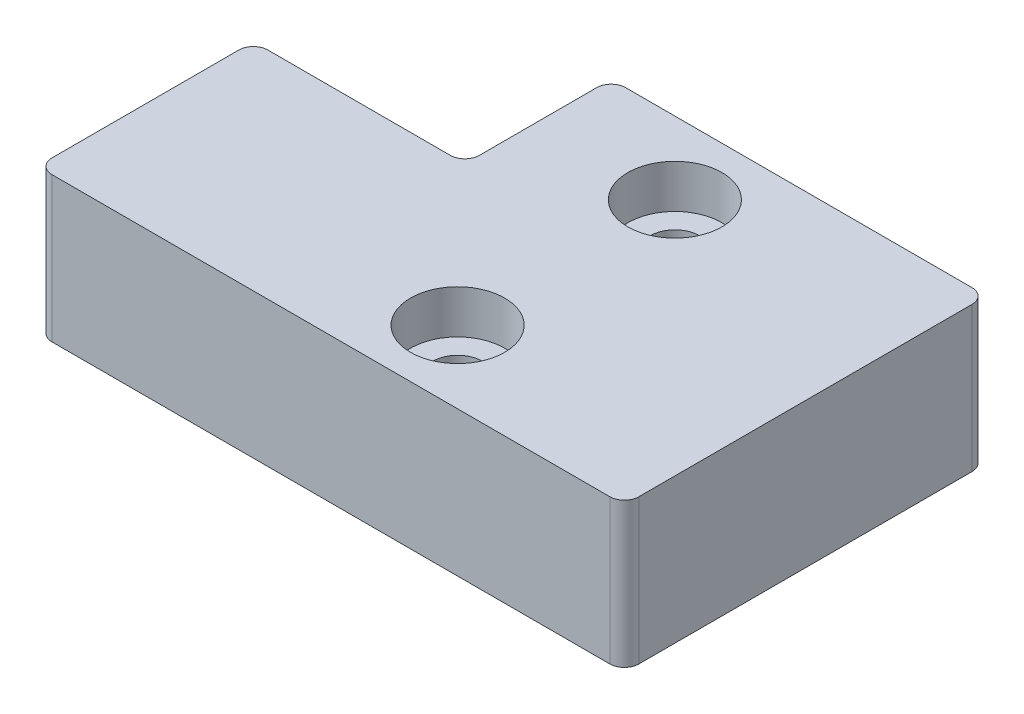
SolidWorks part; units mm, degrees
ref_plane "Front Plane" through (0, 0, 0) normal (0, 0, 1) x (1, 0, 0)
ref_plane "Top Plane" through (0, 0, 0) normal (0, 1, 0) x (1, 0, 0)
ref_plane "Right Plane" through (0, 0, 0) normal (1, 0, 0) x (0, 0, -1)
sketch "Sketch1" plane through (0, 0, 0) normal (0, 1, 0) x (1, 0, 0)
  line L0 (0, 0) -> (40.51, 0)
  line L1 (40.51, 0) -> (40.51, 25)
  line L2 (40.51, 25) -> (14.6, 25)
  line L3 (14.6, 25) -> (14.6, 14.9)
  line L4 (14.6, 14.9) -> (0, 14.9)
  line L5 (0, 14.9) -> (0, 0)
  dimension "D1" = 40.51
  dimension "D2" = 25
  dimension "D3" = 14.6
  dimension "D4" = 10.1
extrude "Boss-Extrude1" add sketch "Sketch1" along normal blind 10
fillet "Fillet1" radius 1 6 edges at (0, 5, -14.9) (14.6, 5, -14.9) (14.6, 5, -25) (40.51, 5, -25) (40.51, 5, 0) (0, 5, 0)
sketch "Sketch2" plane through (0, 10, 0) normal (0, 1, 0) x (1, 0, 0)
  line L0 (24, 25) -> (24, 0) construction
  line L1 (39.51, 25) -> (15.6, 25) construction
  line L2 (1, 0) -> (39.51, 0) construction
  line L3 (40.51, 1) -> (40.51, 24) construction
  line L4 (40.51, 12.5) -> (0, 12.5) construction
  line L5 (0, 13.9) -> (0, 1) construction
  point P12 (24, 20)
  point P13 (24, 5)
  point P14 (24, 12.5)
  dimension "D1" = 16.51
  dimension "D2" = 15
  dimension "D3" = 7.5
hole_wizard "CBORE for M3 SHCS1" positions "Sketch3" profile "Sketch4" counterbore size "M3" standard "ANSI Metric" end condition up to next
sketch "Sketch3" plane through (0, 10, 0) normal (0, 1, 0) x (1, 0, 0)
  point P0 (24, 20)
  point P3 (24, 5)
sketch "Sketch4" plane through (24, 10, -20) normal (1, 0, 0) x (0, 0, 1)
  line L0 (0, 0) -> (0, 10)
  line L1 (0, 10) -> (1.7, 10)
  line L3 (1.7, 10) -> (1.7, 3)
  line L4 (1.7, 3) -> (3.25, 3)
  line L5 (3.25, 3) -> (3.25, 0)
  line L7 (3.25, 0) -> (0, 0)
  line L11 (0, -6.35) -> (0, 107.95) construction
  dimension "Thru Hole Dia." = 3.4
  dimension "Thru Hole Depth" = 10
  dimension "C'Bore Dia." = 6.5
  dimension "C'Bore Depth" = 3
